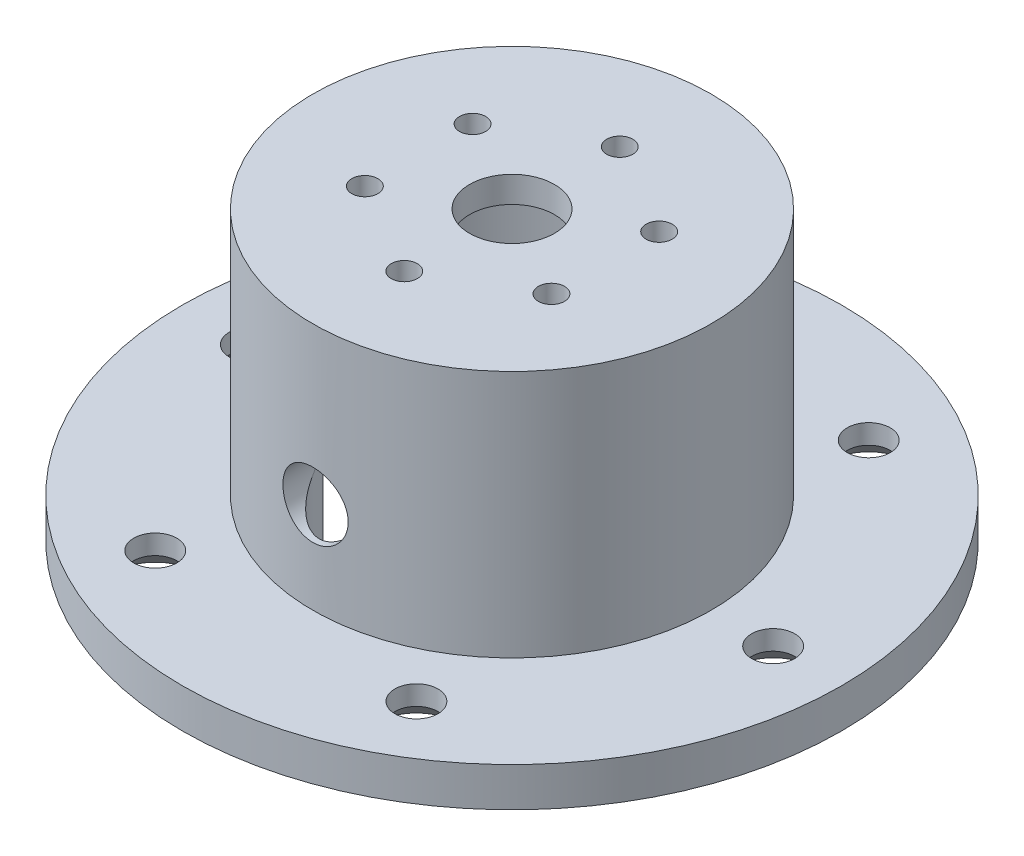
SolidWorks part; units mm, degrees
ref_plane "Front Plane" through (0, 0, 0) normal (0, 0, 1) x (1, 0, 0)
ref_plane "Top Plane" through (0, 0, 0) normal (0, 1, 0) x (1, 0, 0)
ref_plane "Right Plane" through (0, 0, 0) normal (1, 0, 0) x (0, 0, -1)
sketch "Sketch1" plane through (0, 0, 0) normal (0, 0, 1) x (1, 0, 0)
  line L0 (0, -8.7813) -> (0, 7.1563) construction
  line L1 (3.25, 10) -> (3.25, 12)
  line L2 (3.25, 12) -> (15.25, 12)
  line L3 (15.25, 12) -> (15.25, -7)
  line L4 (15.25, -7) -> (25.25, -7)
  line L5 (25.25, -7) -> (25.25, -10)
  line L6 (25.25, -10) -> (12.25, -10)
  line L7 (12.25, -10) -> (12.25, 10)
  line L8 (12.25, 10) -> (3.25, 10)
  point P5 (12.25, 0)
  dimension "D1" = 2
  dimension "D2" = 3
  dimension "D3" = 3
  dimension "D4" = 6.5
  dimension "D5" = 24.5
  dimension "D6" = 20
  dimension "D7" = 10
revolve "Revolve1" add sketch "Sketch1" angle 360 about L0
sketch "Sketch2" plane through (0, 12, 0) normal (0, 1, 0) x (1, 0, 0)
  line L0 (-6.118, 0) -> (7.121, 0) construction
  circle A0 centre (0, 8.25) radius 1
  circle A1 centre (20, 0) radius 1.65
  dimension "D2" = 2
  dimension "D3" = 3.3
  dimension "D1" = 16.5
  dimension "D4" = 20
extrude "Cut-Extrude1" cut sketch "Sketch2" against normal through all
chamfer "Chamfer2" distance 1.5 angle 45 1 edges at (20, -10, 1.65)
pattern_circular "CirPattern1" count 6 over 360 about axis through (0, -8.7813, 0) along (0, -1, 0) of "Cut-Extrude1", "Chamfer2" reverse direction yes
sketch "Sketch3" plane through (0, 0, 0) normal (0, 0, 1) x (1, 0, 0)
  line L0 (-12.25, 10) -> (12.25, 10) construction
  circle A0 centre (0, 0) radius 2.5
  dimension "D2" = 5
  dimension "D1" = 10
extrude "Cut-Extrude2" cut sketch "Sketch3" along normal through all
sketch "Sketch4" plane through (0, -10, 0) normal (0, -1, 0) x (1, 0, 0)
  arc A0 (2.5, 11.9922) -> (-2.5, 11.9922) centre (0, 0) ccw construction
  arc A1 (2.5, 11.9922) -> (-2.5, 11.9922) centre (0, 0) ccw
  arc A2 (2.5, 11.9922) -> (-2.5, 11.9922) centre (0, 12.25) ccw
  point P4 (0, 0)
extrude "Cut-Extrude3" cut sketch "Sketch4" against normal blind 10
